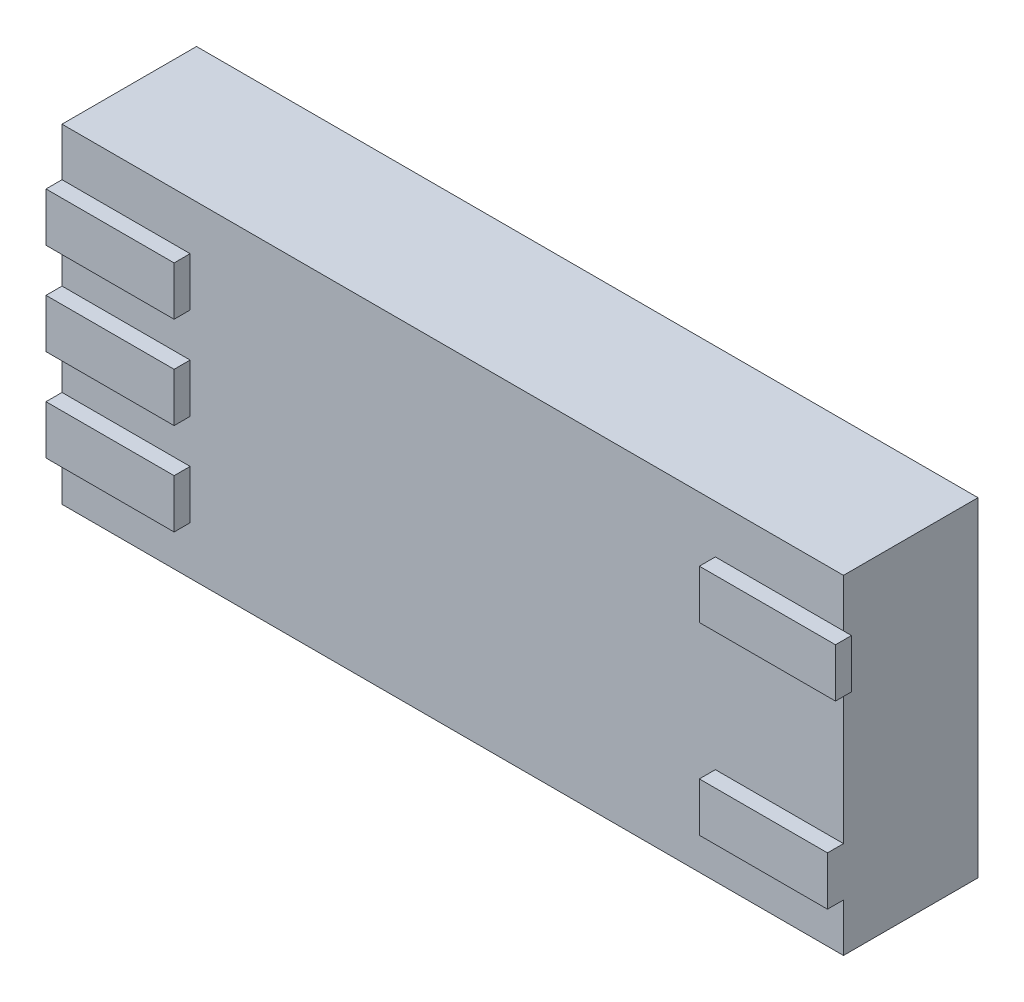
SolidWorks part; units mm, degrees
ref_plane "Front Plane" through (0, 0, 0) normal (0, 0, 1) x (1, 0, 0)
ref_plane "Top Plane" through (0, 0, 0) normal (0, 1, 0) x (1, 0, 0)
ref_plane "Right Plane" through (0, 0, 0) normal (1, 0, 0) x (0, 0, -1)
sketch "Sketch1" plane through (0, 0, 0) normal (0, 0, 1) x (1, 0, 0)
  line L1 (0, 26.1112) -> (61.976, 26.1112)
  line L2 (0, 26.1112) -> (0, 0)
  line L3 (0, 0) -> (61.976, 0)
  line L4 (61.976, 26.1112) -> (61.976, 0)
  dimension "D1" = 61.976
  dimension "D2" = 26.1112
extrude "Boss-Extrude1" add sketch "Sketch1" along normal blind 10.668
sketch "Sketch2" plane through (0, 0, 10.668) normal (0, 0, 1) x (1, 0, 0)
  line L0 (0, 7.6852) -> (10.16, 7.6852)
  line L1 (0, 14.9905) -> (10.16, 14.9905)
  line L2 (0, 14.9905) -> (0, 11.1207)
  line L3 (0, 11.1207) -> (10.16, 11.1207)
  line L4 (10.16, 14.9905) -> (10.16, 11.1207)
  line L5 (0, 7.6852) -> (0, 3.8153)
  line L6 (0, 3.8153) -> (10.16, 3.8153)
  line L7 (10.16, 7.6852) -> (10.16, 3.8153)
  line L8 (0, 22.2959) -> (10.16, 22.2959)
  line L9 (0, 22.2959) -> (0, 18.426)
  line L10 (0, 18.426) -> (10.16, 18.426)
  line L11 (10.16, 22.2959) -> (10.16, 18.426)
  line L12 (51.816, 7.6852) -> (61.976, 7.6852)
  line L13 (51.816, 7.6852) -> (51.816, 3.8153)
  line L14 (51.816, 3.8153) -> (61.976, 3.8153)
  line L15 (61.976, 7.6852) -> (61.976, 3.8153)
  line L16 (61.976, 0) -> (61.976, 26.1112) construction
  line L17 (51.816, 22.2959) -> (61.976, 22.2959)
  line L18 (51.816, 22.2959) -> (51.816, 18.426)
  line L19 (51.816, 18.426) -> (61.976, 18.426)
  line L20 (61.976, 22.2959) -> (61.976, 18.426)
  line L21 (5.08, 26.1112) -> (5.08, 22.2959) construction
  line L22 (5.08, 18.426) -> (5.08, 14.9905) construction
  line L23 (61.976, 26.1112) -> (0, 26.1112) construction
  line L24 (5.08, 3.8153) -> (5.08, 0) construction
  line L25 (0, 26.1112) -> (0, 0) construction
  line L26 (5.08, 11.1207) -> (5.08, 7.6852) construction
  line L27 (0, 0) -> (61.976, 0) construction
  dimension "D1" = 10.16
  dimension "D2" = 3.8153
  dimension "D3" = 3.4355
extrude "Boss-Extrude2" add sketch "Sketch2" along normal blind 1.27
sketch "Sketch3" plane through (61.976, 0, 0) normal (1, 0, 0) x (0, 0, -1)
  line L0 (-11.938, 18.426) -> (-11.938, 22.2959) construction
  line L1 (-11.938, 22.2959) -> (-10.668, 22.2959)
  line L2 (-11.938, 22.2959) -> (-11.938, 18.426)
  line L3 (-11.938, 18.426) -> (-10.668, 18.426)
  line L4 (-10.668, 22.2959) -> (-10.668, 18.426)
  line L5 (-10.668, 7.6852) -> (-10.668, 18.426) construction
extrude "Boss-Extrude3" add sketch "Sketch3" along normal blind 0.635
